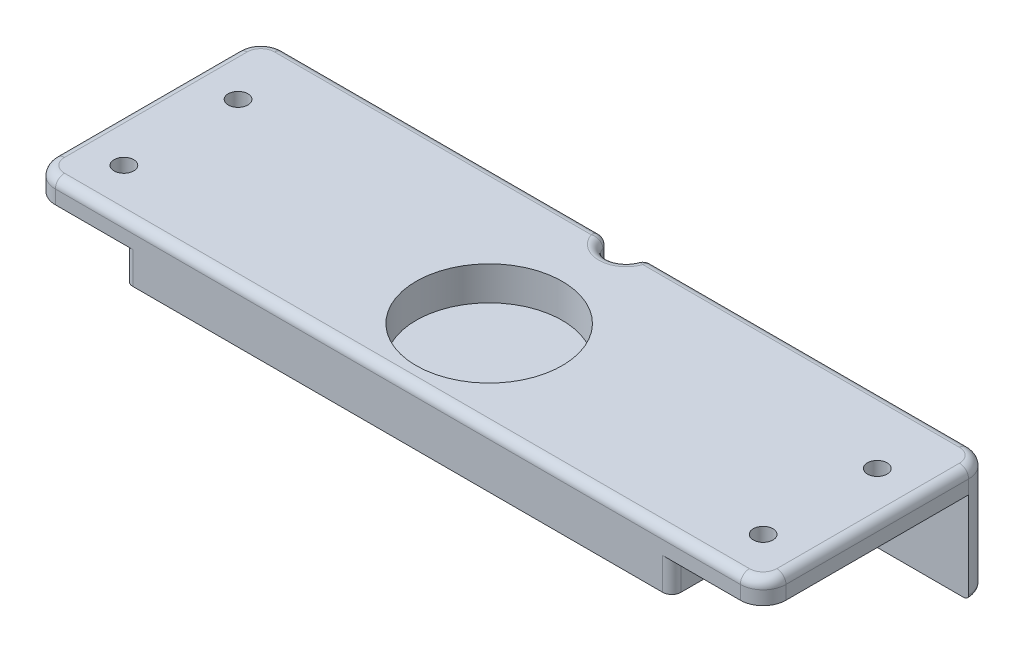
SolidWorks part; units mm, degrees
material "ABS"
ref_plane "Ebene vorne" through (0, 0, 0) normal (0, 0, 1) x (1, 0, 0)
ref_plane "Ebene oben" through (0, 0, 0) normal (0, 1, 0) x (1, 0, 0)
ref_plane "Ebene rechts" through (0, 0, 0) normal (1, 0, 0) x (0, 0, -1)
ref_plane "Ebene1" through (0, 0, 0) normal (0, -1, 0) x (1, 0, 0)
sketch "Skizze1" plane through (0, 0, 0) normal (0, -1, 0) x (1, 0, 0)
  line L0 (80, -30) -> (80, 20)
  line L1 (80, 20) -> (-80, 20)
  line L2 (-80, 20) -> (-80, -30)
  line L3 (-80, -30) -> (80, -30)
extrude "Aufsatz-Linear austragen1" add sketch "Skizze1" against normal blind 25
sketch "Skizze2" plane through (-80, 0, 0) normal (-1, 0, 0) x (0, 0, 1)
  line L0 (20, 13) -> (-22, 13)
  line L1 (-22, 13) -> (-22, 0)
  line L2 (-22, 0) -> (20, 0)
  line L3 (20, 0) -> (20, 13)
extrude "Schnitt-Linear austragen1" cut sketch "Skizze2" against normal through all
sketch "Skizze3" plane through (0, 0, 0) normal (0, -1, 0) x (1, 0, 0)
  line L0 (20, -25) -> (80, -25)
  line L1 (80, -25) -> (80, -22)
  line L2 (80, -22) -> (17, -22)
  arc A0 (17, -22) -> (20, -25) centre (17, -25) cw
extrude "Schnitt-Linear austragen2" cut sketch "Skizze3" against normal blind 13
sketch "Skizze4" plane through (0, 13, 0) normal (0, -1, 0) x (1, 0, 0)
  line L0 (3, -15.7162) -> (3, -22)
  line L1 (3, -22) -> (17, -22)
  line L2 (20, -25) -> (54, -25)
  line L3 (54, -25) -> (54, -8)
  line L4 (54, -8) -> (15.8564, -8)
  arc A0 (15.8564, -8) -> (3, -15.7162) centre (2.1542, 0.2614) cw
  arc A1 (17, -22) -> (20, -25) centre (17, -25) cw
extrude "Schnitt-Linear austragen3" cut sketch "Skizze4" against normal blind 9
sketch "Skizze5" plane through (0, 0, 0) normal (0, -1, 0) x (1, 0, 0)
  line L0 (-80, -22) -> (-80, -25)
  line L1 (-80, -25) -> (-20, -25)
  line L2 (-17, -22) -> (-80, -22)
  arc A0 (-20, -25) -> (-17, -22) centre (-17, -25) cw
extrude "Schnitt-Linear austragen4" cut sketch "Skizze5" against normal blind 13
sketch "Skizze6" plane through (0, 13, 0) normal (0, -1, 0) x (1, 0, 0)
  line L0 (-17, -22) -> (-3, -22)
  line L1 (-3, -22) -> (-3, -15.7162)
  line L2 (-15.8564, -8) -> (-54, -8)
  line L3 (-54, -8) -> (-54, -25)
  line L4 (-54, -25) -> (-20, -25)
  arc A0 (-3, -15.7162) -> (-15.8564, -8) centre (-2.1542, 0.2614) cw
  arc A1 (-20, -25) -> (-17, -22) centre (-17, -25) cw
extrude "Schnitt-Linear austragen5" cut sketch "Skizze6" against normal blind 9
sketch "Skizze7" plane through (0, 0, 20) normal (0, 0, 1) x (1, 0, 0)
  line L0 (-80, 13) -> (-60, 13)
  line L1 (-60, 13) -> (-60, 20)
  line L2 (-60, 20) -> (-80, 20)
  line L3 (-80, 20) -> (-80, 13)
extrude "Schnitt-Linear austragen6" cut sketch "Skizze7" against normal blind 45
sketch "Skizze8" plane through (0, 0, 20) normal (0, 0, 1) x (1, 0, 0)
  line L0 (80, 20) -> (60, 20)
  line L1 (60, 20) -> (60, 13)
  line L2 (60, 13) -> (80, 13)
  line L3 (80, 13) -> (80, 20)
extrude "Schnitt-Linear austragen7" cut sketch "Skizze8" against normal blind 45
sketch "Skizze11" plane through (0, 13, 0) normal (0, -1, 0) x (1, 0, 0)
  line L0 (-54, 14) -> (-54, -2)
  line L1 (-54, -2) -> (-17.8745, -2)
  line L2 (-15.4164, 14) -> (-54, 14)
  arc A0 (-17.8745, -2) -> (-13.0855, 9.2686) centre (6.2724, -5.6102) cw
  arc A1 (-13.0855, 9.2686) -> (-15.4164, 14) centre (-15.4164, 11.0601) ccw
extrude "Schnitt-Linear austragen10" cut sketch "Skizze11" against normal blind 9
sketch "Skizze12" plane through (0, 13, 0) normal (0, -1, 0) x (1, 0, 0)
  line L0 (17.8745, -2) -> (54, -2)
  line L1 (54, -2) -> (54, 14)
  line L2 (54, 14) -> (15.4164, 14)
  arc A0 (13.5079, 10.9573) -> (17.8745, -2) centre (-35.7296, -12.85) cw
  arc A1 (15.4164, 14) -> (13.5079, 10.9573) centre (15.4164, 11.8801) ccw
extrude "Schnitt-Linear austragen11" cut sketch "Skizze12" against normal blind 9
hole_wizard "Ø5.8 (5.8) Durchmesser Bohrung1" positions "Skizze16" profile "Skizze15" hole size "Ø5.8" standard "ANSI Metrisch"
sketch "Skizze16" plane through (0, 25, 0) normal (0, 1, 0) x (1, 0, 0)
  point P0 (-70, -10)
  point P1 (70, -10)
  point P2 (-70, 15)
  point P3 (70, 15)
sketch "Skizze15" plane through (-70, 25, 10) normal (1, 0, 0) x (0, 0, 1)
  line L0 (0, 0) -> (0, 25)
  line L1 (0, 25) -> (2.15, 25)
  line L2 (2.15, 25) -> (2.15, 0)
  line L5 (2.15, 0) -> (0, 0)
  line L11 (0, -6.35) -> (0, 107.95) construction
  dimension "Bohrerdurchmesser" = 4.3
  dimension "Bohrungstiefe" = 25
hole_wizard "Ø8.0 (8) Durchmesser Bohrung1" positions "Skizze20" profile "Skizze19" hole size "Ø8.0" standard "ANSI Metrisch"
sketch "Skizze20" plane through (0, 25, 0) normal (0, 1, 0) x (1, 0, 0)
  point P0 (0, 30)
sketch "Skizze19" plane through (0, 25, -30) normal (1, 0, 0) x (0, 0, 1)
  line L0 (0, 0) -> (0, 25)
  line L1 (0, 25) -> (4, 25)
  line L2 (4, 25) -> (4, 0)
  line L5 (4, 0) -> (0, 0)
  line L11 (0, -6.35) -> (0, 107.95) construction
  dimension "Bohrerdurchmesser" = 8
  dimension "Bohrungstiefe" = 25
hole_wizard "Ø4.5 (4.5) Durchmesser Bohrung1" positions "Skizze22" profile "Skizze21" hole size "Ø4.5" standard "ANSI Metrisch" end condition up to next
sketch "Skizze22" plane through (0, 0, -30) normal (0, 0, -1) x (-1, 0, 0)
  point P0 (10.125, 12.5)
  point P1 (-10.125, 12.5)
sketch "Skizze21" plane through (-10.125, 12.5, -30) normal (1, 0, 0) x (0, 1, 0)
  line L0 (0, 0) -> (0, 8)
  line L1 (0, 8) -> (2.15, 8)
  line L2 (2.15, 8) -> (2.15, 0)
  line L5 (2.15, 0) -> (0, 0)
  line L11 (0, -6.35) -> (0, 107.95) construction
  dimension "Bohrerdurchmesser" = 4.3
  dimension "Bohrungstiefe" = 8
hole_wizard "Ø16.0 (16) Durchmesser Bohrung1" positions "Skizze24" profile "Skizze23" hole size "Ø16.0" standard "ANSI Metrisch"
sketch "Skizze24" plane through (0, 13, 0) normal (0, -1, 0) x (-1, 0, 0)
  point P0 (0, 0)
sketch "Skizze23" plane through (0, 13, 0) normal (1, 0, 0) x (0, 0, -1)
  line L0 (0, 0) -> (0, 4.476)
  line L1 (0, 4.476) -> (8, 4.476)
  line L2 (8, 4.476) -> (8, 0)
  line L5 (8, 0) -> (0, 0)
  line L10 (0, 4.476) -> (-8, 4.476) construction
  line L11 (0, -6.35) -> (0, 107.95) construction
  dimension "Bohrerdurchmesser" = 16
  dimension "Bohrungstiefe" = 4.476
  dimension "Spitzenwinkel" = 180
fillet "Verrundung1" radius 5 4 edges at (80, 22.5, 20) (80, 12.5, -30) (-80, 22.5, 20) (-80, 12.5, -30) tangent propagation no
fillet "Verrundung2" radius 2 28 edges at (3, 17.5, -15.7162) (54, 17.5, 14) (-60, 16.5, 20) (17.8745, 17.5, -2) (-54, 17.5, -2) (54, 17.5, -8) (15.8564, 17.5, -8) (-15.8564, 17.5, -8) (60, 16.5, 20) (-54, 17.5, -8) (-54, 17.5, 14) (-54, 17.5, -25) (-17.8745, 17.5, -2) (-3, 17.5, -15.7162) (54, 17.5, -2) (54, 17.5, -25) (0, 25, -26) (-4, 12.5, -30) (4, 12.5, -30) (-39.5, 25, -30) (-78.5355, 25, -28.5355) (-80, 25, -5) (-78.5355, 25, 18.5355) (0, 25, 20) (78.5355, 25, 18.5355) (39.5, 25, -30) (80, 25, -5) (78.5355, 25, -28.5355)
chamfer "Fase1" distance 7 angle 45 1 edges at (0, 13, -22)
fillet "Verrundung3" radius 1 9 edges at (-78.5355, 0, -28.5355) (-40.3284, 0, -30) (-4.5022, 0, -29.633) (0, 0, -26) (4.5022, 0, -29.633) (78.5355, 0, -28.5355) (40.3284, 0, -30) (-3, 14, -22) (3, 14, -22) tangent propagation no
sketch "Skizze26" plane through (0, 25, 0) normal (0, 1, 0) x (1, 0, 0)
  circle A0 centre (0, 0) radius 16
extrude "Schnitt-Linear austragen13" cut sketch "Skizze26" against normal blind 7.4
sketch "Skizze27" plane through (0, 0, -22) normal (0, 0, 1) x (1, 0, 0)
  line L1 (14.3974, 12.5) -> (12.2612, 16.2)
  line L2 (12.2612, 16.2) -> (7.9888, 16.2)
  line L3 (7.9888, 16.2) -> (5.8526, 12.5)
  line L4 (5.8526, 12.5) -> (7.9888, 8.8)
  line L5 (7.9888, 8.8) -> (12.2612, 8.8)
  line L6 (12.2612, 8.8) -> (14.3974, 12.5)
  line L7 (-5.8526, 12.5) -> (-7.9888, 16.2)
  line L8 (-7.9888, 16.2) -> (-12.2612, 16.2)
  line L9 (-12.2612, 16.2) -> (-14.3974, 12.5)
  line L10 (-14.3974, 12.5) -> (-12.2612, 8.8)
  line L11 (-12.2612, 8.8) -> (-7.9888, 8.8)
  line L12 (-7.9888, 8.8) -> (-5.8526, 12.5)
  circle A0 centre (10.125, 12.5) radius 3.7 construction
  circle A1 centre (-10.125, 12.5) radius 3.7 construction
extrude "Schnitt-Linear austragen14" cut sketch "Skizze27" against normal blind 4
equation "\"M4_mutter\"= 7.4mm"
equation "\"M4_loch\"= 4.3mm"
equation "\"Bohrerdurchmesser@Skizze15\"= \"M4_loch\""
equation "\"Bohrerdurchmesser@Skizze21\"=\"M4_loch\""
equation "\"M8_loch\"= 8.4mm"
